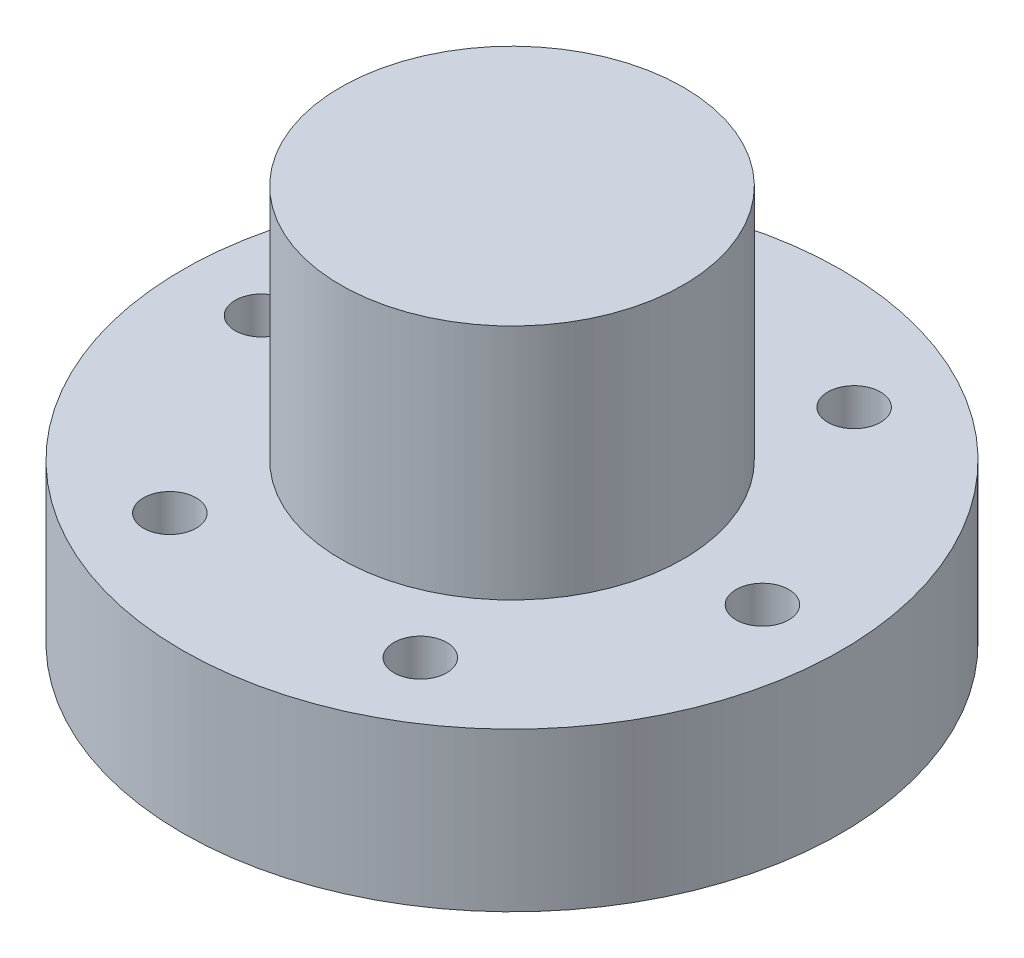
SolidWorks part; units mm, degrees
ref_plane "Plan de face" through (0, 0, 0) normal (0, 0, 1) x (1, 0, 0)
ref_plane "Plan de dessus" through (0, 0, 0) normal (0, 1, 0) x (1, 0, 0)
ref_plane "Plan de droite" through (0, 0, 0) normal (1, 0, 0) x (0, 0, -1)
sketch "Esquisse1" plane through (0, 0, 0) normal (0, 0, 1) x (1, 0, 0)
  line L0 (6.5, 15) -> (6.5, 6)
  line L1 (6.5, 6) -> (12.5, 6)
  line L2 (12.5, 6) -> (12.5, 0)
  line L6 (12.5, 0) -> (0, 0)
  line L7 (0, 0) -> (0, 15)
  line L8 (0, 15) -> (6.5, 15)
  dimension "D1" = 12.5
  dimension "D2" = 6
  dimension "D3" = 15
  dimension "D4" = 6.5
revolve "Révolution2" add sketch "Esquisse1" angle 360 about L7
sketch "Esquisse3" plane through (0, 6, 0) normal (0, 1, 0) x (1, 0, 0)
  line L0 (0, 0) -> (9.5, 0) construction
  circle A0 centre (9.5, 0) radius 1
  circle A1 centre (4.75, -8.2272) radius 1
  circle A2 centre (0, 0) radius 12.5 construction
  circle A3 centre (0, 0) radius 6.5 construction
  circle A4 centre (-4.75, -8.2272) radius 1
  circle A5 centre (-9.5, 0) radius 1
  circle A6 centre (-4.75, 8.2272) radius 1
  circle A7 centre (4.75, 8.2272) radius 1
  point P7 (6.5, 0)
  point P8 (12.5, 0)
  point P23 (0, 0)
  dimension "D1" = 2
  dimension "D3" = 3
  dimension "D2" = 3
  dimension "D4" = 6
extrude "Enlèv. mat.-Extru.1" cut sketch "Esquisse3" against normal through all
